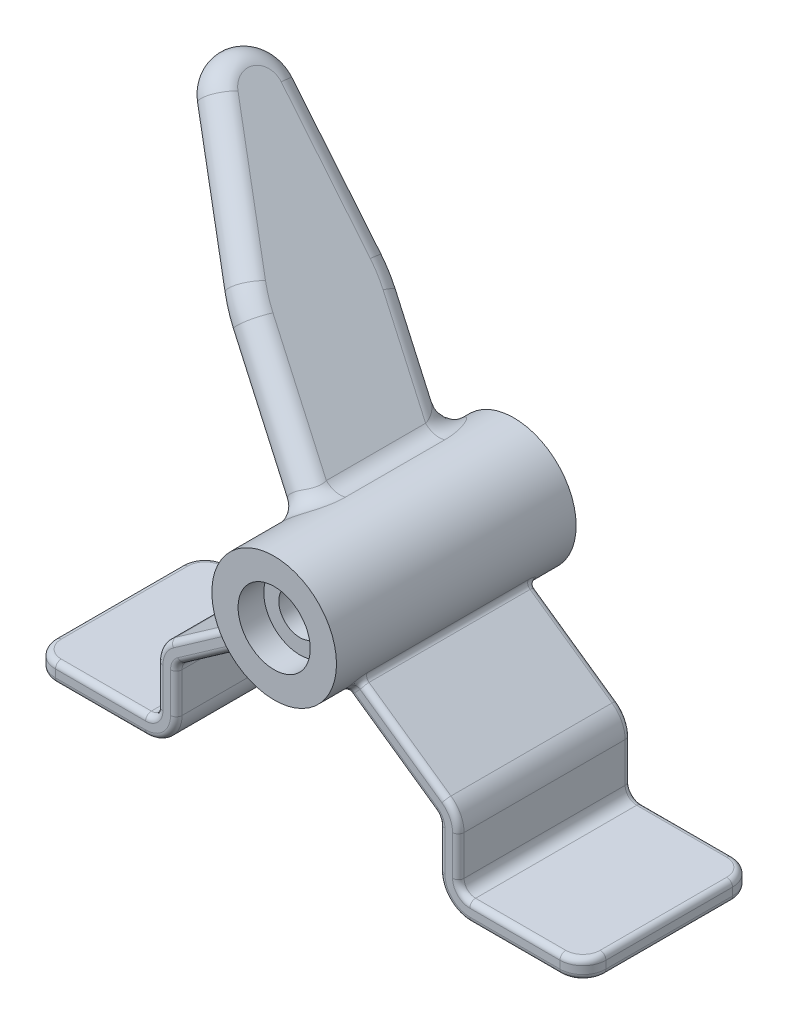
SolidWorks part; units mm, degrees
ref_plane "Front Plane" through (0, 0, 0) normal (0, 0, 1) x (1, 0, 0)
ref_plane "Top Plane" through (0, 0, 0) normal (0, 1, 0) x (1, 0, 0)
ref_plane "Right Plane" through (0, 0, 0) normal (1, 0, 0) x (0, 0, -1)
sketch "Sketch1" plane through (0, 0, 0) normal (0, 0, 1) x (1, 0, 0)
  circle A0 centre (0, 0) radius 32.5
  dimension "D1" = 65
extrude "Boss-Extrude1" add sketch "Sketch1" along normal mid plane 125
sketch "Sketch2" plane through (0, 0, 0) normal (0, 0, 1) x (1, 0, 0)
  line L0 (0, 0) -> (78.5481, -55)
  line L1 (78.5481, -55) -> (78.5481, -90)
  line L2 (78.5481, -90) -> (143.5481, -90)
  dimension "D1" = 125
  dimension "D2" = 65
  dimension "D3" = 35
  dimension "D4" = 90
extrude "Extrude-Thin1" add sketch "Sketch2" along normal mid plane 90 thin thin type one direction wall 10
fillet "Fillet1" radius 12 2 edges at (143.5481, -95, -45) (143.5481, -95, 45)
fillet "Fillet2" radius 3 26 edges at (42.7924, -42.1713, -45) (67.8702, -60.5586, -45) (68.5481, -73.6645, -45) (73.2344, -95.3137, -45) (108.0481, -100, -45) (140.0334, -100, -41.4853) (143.5481, -100, 0) (140.0334, -100, 41.4853) (108.0481, -100, 45) (73.2344, -95.3137, 45) (68.5481, -73.6645, 45) (67.8702, -60.5586, 45) (49.1739, -34.4319, -45) (76.7403, -55.9411, -45) (78.5481, -73.6645, -45) (80.3055, -88.2426, -45) (108.0481, -90, -45) (140.0334, -90, -41.4853) (143.5481, -90, 0) (140.0334, -90, 41.4853) (108.0481, -90, 45) (80.3055, -88.2426, 45) (78.5481, -73.6645, 45) (76.7403, -55.9411, 45) (42.7924, -42.1713, 45) (49.1739, -34.4319, 45)
fillet "Fillet3" radius 3 8 edges at (25.9586, -19.5551, 44.3454) (23.4308, -22.5222, 45) (20.0999, -25.5391, 43.8112) (19.5951, -25.9284, 0) (20.4878, -25.229, -44.3092) (23.4308, -22.5222, -45) (26.24, -19.1758, -43.8739) (26.6224, -18.6412, 0)
mirror "Mirror1" about plane through (0, 0, 0) normal (1, 0, 0) of "Fillet3", "Fillet1", "Fillet2", "Extrude-Thin1"
ref_plane "45" through (0, 0, 0) normal (0.7071, 0.7071, 0) x (0, 0, -1)
sketch "Sketch3" plane through (0, 0, 0) normal (0.7071, 0.7071, 0) x (0, 0, -1)
  line L0 (0, 0) -> (137.7361, 0) construction
  line L1 (-48, 0) -> (48, 0) construction
  line L2 (0, 0) -> (46.5874, 173.8666) construction
  line L3 (-36.2347, 0) -> (-8.5062, 103.4842)
  line L4 (-3.4523, 116.9895) -> (28.6166, 182.6444)
  line L5 (61.4845, 99.5897) -> (66.5395, 172.483)
  line L6 (36.2347, 0) -> (59.1087, 85.3669)
  line L7 (36.2347, 0) -> (-36.2347, 0)
  line L8 (-6.6314, 110.4809) -> (27.176, 101.4222) construction
  arc A0 (28.6166, 182.6444) -> (66.5395, 172.483) centre (46.5874, 173.8666) cw
  arc A1 (61.4845, 99.5897) -> (59.1087, 85.3669) centre (-13.3358, 104.7783) cw
  arc A2 (-8.5062, 103.4842) -> (-3.4523, 116.9895) centre (63.9383, 84.0728) cw
  point P15 (60.9834, 92.3635)
  point P18 (-6.6314, 110.4809)
  dimension "D2" = 75
  dimension "D5" = 20
  dimension "D1" = 75
  dimension "D3" = 70
  dimension "D4" = 75
  dimension "D6" = 180
extrude "Boss-Extrude2" add sketch "Sketch3" along normal mid plane 20
fillet "Fillet4" 2 edges at (-40.4492, 54.5913, 18.2275) (-54.5913, 40.4492, 18.2275) type full round first side face at (-67.0063, 81.1485, -28.0707) second side face at (-81.1485, 67.0063, -28.0707) middle face at (-47.799, 47.799, 18.1219)
fillet "Fillet5" radius 10 4 edges at (-22.981, 22.981, 27.5263) (-28.9371, 14.795, -8.2859) (-22.981, 22.981, -44.943) (-14.795, 28.9371, -8.2859)
hole_wizard "CBORE for M20 Hex Head Bolt1" positions "Sketch5" profile "Sketch4" counterbore size "M20" standard "ANSI Metric" end condition through all
sketch "Sketch5" plane through (0, 0, 62.5) normal (0, 0, 1) x (1, 0, 0)
  point P0 (0, 0)
sketch "Sketch4" plane through (0, 0, 62.5) normal (1, 0, 0) x (0, -1, 0)
  line L0 (0, 0) -> (0, 129.0874)
  line L1 (0, 129.0874) -> (11, 129.0874)
  line L3 (11, 129.0874) -> (11, 13.4)
  line L4 (11, 13.4) -> (18.82, 13.4)
  line L5 (18.82, 13.4) -> (18.82, 0)
  line L7 (18.82, 0) -> (0, 0)
  line L11 (0, -6.35) -> (0, 107.95) construction
  dimension "Thru Hole Dia." = 22
  dimension "Thru Hole Depth" = 129.0874
  dimension "C'Bore Dia." = 37.64
  dimension "C'Bore Depth" = 13.4
